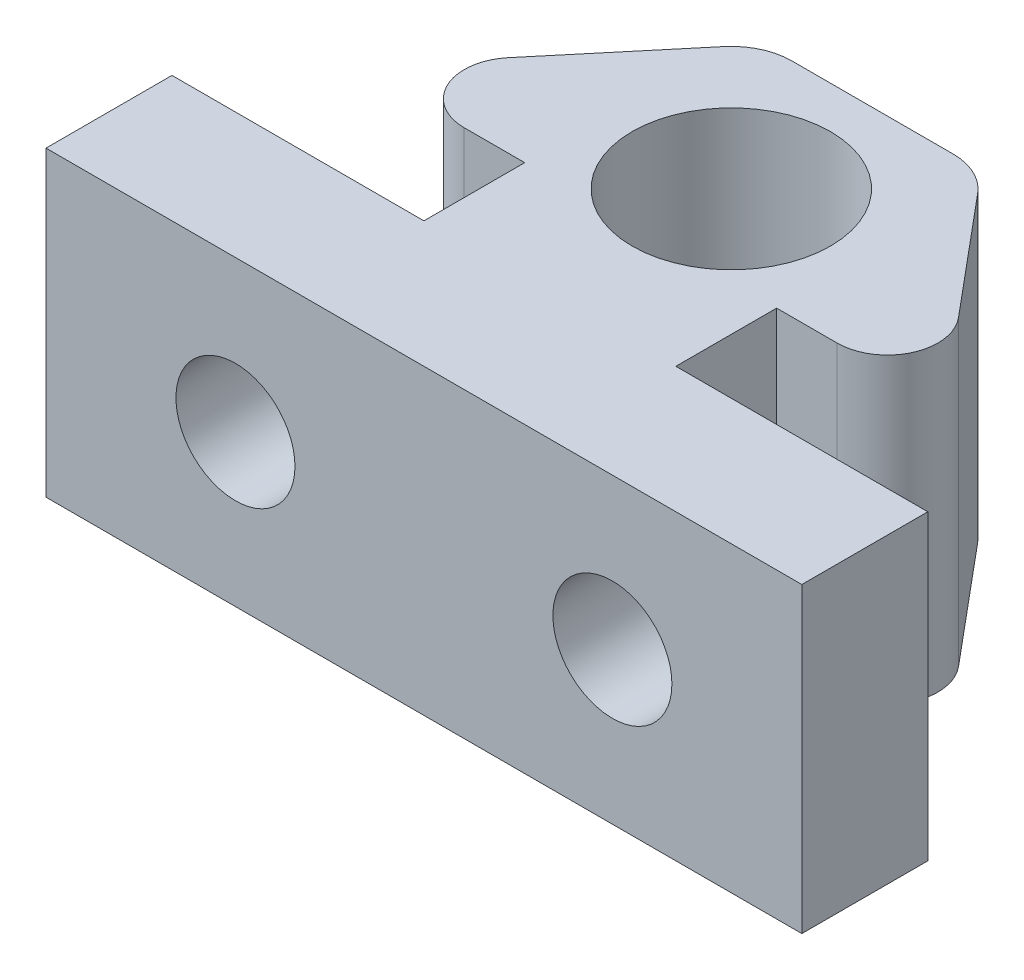
SolidWorks part; units mm, degrees
ref_plane "Front Plane" through (0, 0, 0) normal (0, 0, 1) x (1, 0, 0)
ref_plane "Top Plane" through (0, 0, 0) normal (0, 1, 0) x (1, 0, 0)
ref_plane "Right Plane" through (0, 0, 0) normal (1, 0, 0) x (0, 0, -1)
sketch "Sketch1" plane through (0, 0, 0) normal (0, 0, 1) x (1, 0, 0)
  line L0 (-9.525, 0) -> (9.525, 0) construction
  line L1 (-9.525, -3.81) -> (9.525, -3.81)
  line L2 (-9.525, -3.81) -> (-9.525, 3.81)
  line L3 (-9.525, 3.81) -> (9.525, 3.81)
  line L4 (9.525, -3.81) -> (9.525, 3.81)
  line L5 (-9.525, -3.81) -> (9.525, 3.81) construction
  line L6 (-9.525, 3.81) -> (9.525, -3.81) construction
  line L8 (-9.525, 3.81) -> (0, 3.81)
  point P0 (0, 0)
  dimension "D1" = 7.62
  dimension "D2" = 19.05
extrude "Boss-Extrude1" add sketch "Sketch1" along normal blind 3.175 contours L2 L1 L4 L3
sketch "Sketch2" plane through (0, 3.81, 0) normal (0, 1, 0) x (1, 0, 0)
  line L0 (0, 0) -> (0, 8.128) construction
  line L1 (3.175, 0) -> (3.175, 2.54)
  line L2 (-9.525, 0) -> (9.525, 0) construction
  line L3 (3.175, 2.54) -> (4.6994, 2.54)
  line L4 (5.6737, 4.6247) -> (3.2011, 7.5816)
  line L5 (2.032, 8.128) -> (-2.032, 8.128)
  line L6 (3.175, 0) -> (-3.175, 0)
  line L7 (-3.175, 0) -> (-3.175, 2.54)
  line L8 (-3.175, 2.54) -> (-4.6994, 2.54)
  line L9 (-5.6737, 4.6247) -> (-3.2011, 7.5816)
  arc A0 (3.2011, 7.5816) -> (2.032, 8.128) centre (2.032, 6.604) ccw
  arc A1 (4.6994, 2.54) -> (5.6737, 4.6247) centre (4.6994, 3.81) ccw
  arc A2 (-4.6994, 2.54) -> (-5.6737, 4.6247) centre (-4.6994, 3.81) cw
  arc A3 (-3.2011, 7.5816) -> (-2.032, 8.128) centre (-2.032, 6.604) cw
  point P19 (2.7442, 8.128)
  point P22 (7.4168, 2.54)
  point P25 (-7.4168, 2.54)
  point P28 (-2.7442, 8.128)
  dimension "D5" = 1.524
  dimension "D7" = 1.27
  dimension "D1" = 8.128
  dimension "D2" = 6.35
  dimension "D3" = 5.588
  dimension "D4" = 14.8336
  dimension "D6" = 4.064
extrude "Boss-Extrude2" add sketch "Sketch2" against normal up to surface (7.62 mm away) up to face at (0, -3.81, 1.5875)
sketch "Sketch3" plane through (0, 0, 3.175) normal (0, 0, 1) x (1, 0, 0)
  line L0 (0, 3.81) -> (0, -3.81) construction
  line L1 (-9.525, 3.81) -> (9.525, 3.81) construction
  line L2 (-9.525, -3.81) -> (9.525, -3.81) construction
  circle A0 centre (-4.75, 0) radius 1.5
  circle A1 centre (4.75, 0) radius 1.5
  dimension "D2" = 3
  dimension "D1" = 9.5
extrude "Cut-Extrude1" cut sketch "Sketch3" against normal up to surface (3.175 mm away) up to face at (6.35, 0, 0)
sketch "Sketch4" plane through (0, -3.81, 0) normal (0, -1, 0) x (-1, 0, 0)
  line L0 (0, -3.175) -> (0, 8.128) construction
  line L1 (9.525, -3.175) -> (-9.525, -3.175) construction
  line L2 (2.032, 8.128) -> (-2.032, 8.128) construction
  circle A0 centre (0, 4.572) radius 2.5
  point P9 (0, 4.572)
  dimension "D1" = 5
  dimension "D2" = 4.572
extrude "Cut-Extrude2" cut sketch "Sketch4" against normal through all
